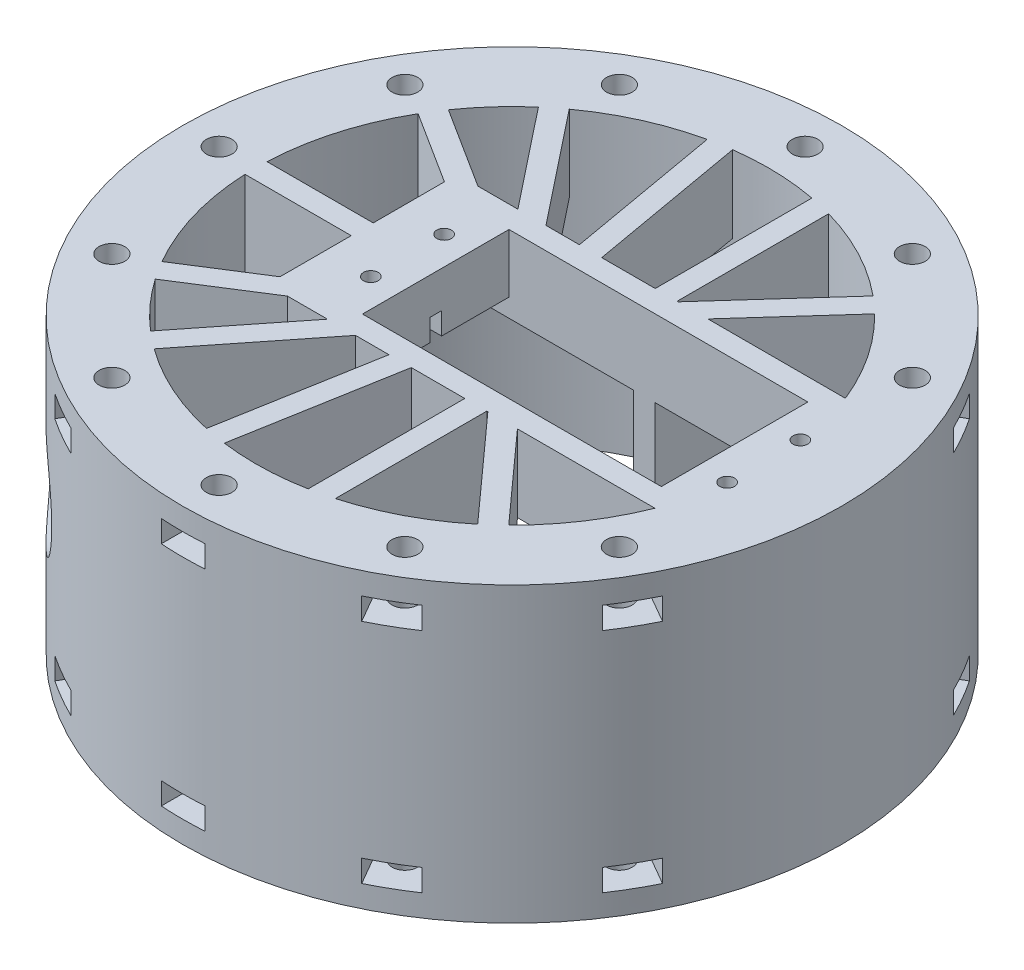
SolidWorks part; units mm, degrees
ref_plane "Front Plane" through (0, 0, 0) normal (0, 0, 1) x (1, 0, 0)
ref_plane "Top Plane" through (0, 0, 0) normal (0, 1, 0) x (1, 0, 0)
ref_plane "Right Plane" through (0, 0, 0) normal (1, 0, 0) x (0, 0, -1)
sketch "Sketch1" plane through (0, 0, 0) normal (0, 1, 0) x (1, 0, 0)
  line L0 (-43.0464, 0) -> (41.9462, 0) construction
  line L1 (0, 43.1152) -> (0, -41.8775) construction
  circle A1 centre (0, 0) radius 45
  dimension "D2" = 90
extrude "Boss-Extrude1" add sketch "Sketch1" along normal blind 40
sketch "Sketch2" plane through (0, 0, 0) normal (0, -1, 0) x (1, 0, 0)
  circle A0 centre (0, 0) radius 35
  dimension "D1" = 70
extrude "Cut-Extrude1" cut sketch "Sketch2" against normal blind 29.5
sketch "Sketch3" plane through (0, 29.5, 0) normal (0, -1, 0) x (1, 0, 0)
  line L0 (35, 0) -> (-35, 0) construction
  line L1 (0, -35) -> (0, 35) construction
  line L3 (37.5324, -10) -> (-17.4676, -10)
  line L4 (37.5324, -10) -> (37.5324, 10)
  line L5 (37.5324, 10) -> (-17.4676, 10)
  line L6 (-17.4676, -10) -> (-17.4676, 10)
  circle A0 centre (0, 0) radius 35 construction
  circle A1 centre (0, 0) radius 35 construction
  dimension "D1" = 20
  dimension "D2" = 55
  dimension "D3" = 10
  dimension "D4" = 37.5324
extrude "Cut-Extrude2" cut sketch "Sketch3" against normal blind 2.5 and the other way up to next
sketch "Sketch4" plane through (0, 32, 0) normal (0, -1, 0) x (1, 0, 0)
  line L0 (37.5324, 0) -> (-17.4676, 0) construction
  line L1 (37.5324, 10) -> (37.5324, -10) construction
  line L2 (-17.4676, 10) -> (-17.4676, -10) construction
  line L3 (0, -10) -> (0, 10) construction
  line L4 (-17.4676, -10) -> (33.541, -10) construction
  line L5 (33.541, 10) -> (-17.4676, 10) construction
  line L7 (30.3722, -10) -> (-10.4278, -10)
  line L8 (30.3722, -10) -> (30.3722, 10)
  line L9 (30.3722, 10) -> (-10.4278, 10)
  line L10 (-10.4278, -10) -> (-10.4278, 10)
  dimension "D1" = 20
  dimension "D2" = 40.8
  dimension "D3" = 30.3722
  dimension "D4" = 10
extrude "Cut-Extrude3" cut sketch "Sketch4" against normal blind 9
sketch "Sketch8" plane through (0, 29.5, 0) normal (0, -1, 0) x (1, 0, 0)
  line L0 (-17.4676, 0) -> (-35, 0) construction
  line L1 (-17.4676, 10) -> (-17.4676, -10) construction
  line L2 (8.0367, 10) -> (8.0367, 34.0648) construction
  line L3 (33.541, 10) -> (-17.4676, 10) construction
  line L4 (8.0367, -10) -> (8.0367, -29.3194) construction
  line L5 (-17.4676, -10) -> (33.541, -10) construction
  line L6 (6.5367, 10) -> (6.5367, 34.3842)
  line L7 (9.5367, 10) -> (9.5367, 33.6757)
  line L8 (9.5367, 10) -> (6.5367, 10)
  line L9 (9.5367, -10) -> (6.5367, -10)
  line L10 (6.5367, -10) -> (6.5367, -34.3842)
  line L11 (9.5367, -10) -> (9.5367, -33.6757)
  line L12 (-17.4676, 1.5) -> (-34.9678, 1.5)
  line L13 (-17.4676, -1.5) -> (-34.9678, -1.5)
  line L14 (-17.4676, 1.5) -> (-17.4676, -1.5)
  arc A0 (33.541, 10) -> (33.541, -10) centre (0, 0) ccw construction
  arc A1 (9.5367, 33.6757) -> (6.5367, 34.3842) centre (7.9531, 33.6757) ccw
  arc A2 (9.5367, -33.6757) -> (6.5367, -34.3842) centre (7.9531, -33.6757) cw
  arc A3 (-34.9678, 1.5) -> (-34.9678, -1.5) centre (-34.9678, 0) ccw
  dimension "D3" = 1.5
  dimension "D1" = 1.5
  dimension "D2" = 1.5
  dimension "D4" = 1.5
extrude "Boss-Extrude2" add sketch "Sketch8" along normal through all
sketch "Sketch16" plane through (0, 32, 0) normal (0, -1, 0) x (1, 0, 0)
  line L0 (-17.4676, 0) -> (37.5324, 0) construction
  line L1 (-17.4676, 10) -> (-17.4676, -10) construction
  line L2 (37.5324, -10) -> (37.5324, 10) construction
  line L3 (30.3722, -0.8) -> (37.5324, -0.8)
  line L4 (-10.4278, -0.8) -> (-17.4676, -0.8)
  line L5 (-10.4278, 10) -> (-10.4278, -10) construction
  line L6 (-10.4278, 0.8) -> (-17.4676, 0.8)
  line L7 (-17.4676, 0.8) -> (-17.4676, -0.8)
  line L8 (-10.4278, 0.8) -> (-10.4278, -0.8)
  line L9 (30.3722, -10) -> (30.3722, 10) construction
  line L10 (30.3722, 0.8) -> (37.5324, 0.8)
  line L11 (37.5324, 0.8) -> (37.5324, -0.8)
  line L12 (30.3722, 0.8) -> (30.3722, -0.8)
  dimension "D1" = 0.8
extrude "Cut-Extrude10" cut sketch "Sketch16" against normal blind 3
sketch "Sketch27" plane through (0, 0, 0) normal (0, -1, 0) x (1, 0, 0)
  line L0 (0, 0) -> (0, -53.17) construction
  line L1 (0, 0) -> (47.7582, -27.5732) construction
  line L3 (31.641, -18.2679) -> (31.641, -21.7321) construction
  line L4 (31.641, -21.7321) -> (34.641, -23.4641) construction
  line L5 (34.641, -23.4641) -> (37.641, -21.7321) construction
  line L6 (37.641, -21.7321) -> (37.641, -18.2679) construction
  line L7 (37.641, -18.2679) -> (34.641, -16.5359) construction
  line L8 (34.641, -16.5359) -> (31.641, -18.2679) construction
  circle A0 centre (0, 0) radius 40 construction
  circle A1 centre (34.641, -20) radius 1.75
  circle A2 centre (0, 0) radius 35 construction
  circle A3 centre (34.641, -20) radius 3 construction
  circle A4 centre (20, -34.641) radius 1.75
  circle A5 centre (0, -40) radius 1.75
  circle A6 centre (-20, -34.641) radius 1.75
  circle A7 centre (-34.641, -20) radius 1.75
  circle A8 centre (-40, 0) radius 1.75
  circle A9 centre (-34.641, 20) radius 1.75
  circle A10 centre (-20, 34.641) radius 1.75
  circle A11 centre (0, 40) radius 1.75
  circle A12 centre (20, 34.641) radius 1.75
  circle A13 centre (34.641, 20) radius 1.75
  circle A15 centre (40, 0) radius 1.75 [skipped]
  point P28 (0, 0)
  point P41 (0, 0)
  dimension "D1" = 80
  dimension "D3" = 3.5
  dimension "D4" = 70
  dimension "D5" = 6
  dimension "D6" = 12
  dimension "D2" = 60
extrude "Cut-Extrude15" cut sketch "Sketch27" against normal through all
ref_plane "Plane1" through (0, 37, 0) normal (0, 1, 0) x (1, 0, 0)
sketch "Sketch28" plane through (0, 37, 0) normal (0, 1, 0) x (1, 0, 0)
  line L0 (0, 0) -> (-54.493, 0) construction
  line L1 (-31.641, 18.2679) -> (-31.641, 21.7321)
  line L2 (-36.5359, 0) -> (-38.2679, 3)
  line L3 (-38.2679, 3) -> (-44.8999, 3)
  line L4 (-31.641, 21.7321) -> (-37.3844, 25.048)
  line L5 (-40.3844, 19.8519) -> (-34.641, 16.5359)
  line L6 (-44.8999, -3) -> (-38.2679, -3)
  line L7 (-38.2679, -3) -> (-36.5359, 0)
  line L8 (-43.4641, 0) -> (-42.5981, -1.5) [skipped]
  line L9 (-41.7321, 3) -> (-42.5981, 1.5) [skipped]
  line L10 (-34.641, 16.5359) -> (-31.641, 18.2679)
  line L11 (-18.2679, 31.641) -> (-16.5359, 34.641)
  line L12 (-16.5359, 34.641) -> (-19.8519, 40.3844)
  line L13 (-25.048, 37.3844) -> (-21.7321, 31.641)
  line L14 (-21.7321, 31.641) -> (-18.2679, 31.641)
  line L15 (0, 36.5359) -> (3, 38.2679)
  line L16 (3, 38.2679) -> (3, 44.8999)
  line L17 (-3, 44.8999) -> (-3, 38.2679)
  line L18 (-3, 38.2679) -> (0, 36.5359)
  line L19 (18.2679, 31.641) -> (21.7321, 31.641)
  line L20 (21.7321, 31.641) -> (25.048, 37.3844)
  line L21 (19.8519, 40.3844) -> (16.5359, 34.641)
  line L22 (16.5359, 34.641) -> (18.2679, 31.641)
  line L23 (31.641, 18.2679) -> (34.641, 16.5359)
  line L24 (34.641, 16.5359) -> (40.3844, 19.8519)
  line L25 (37.3844, 25.048) -> (31.641, 21.7321)
  line L26 (31.641, 21.7321) -> (31.641, 18.2679)
  line L31 (31.641, -18.2679) -> (31.641, -21.7321)
  line L32 (31.641, -21.7321) -> (37.3844, -25.048)
  line L33 (40.3844, -19.8519) -> (34.641, -16.5359)
  line L34 (34.641, -16.5359) -> (31.641, -18.2679)
  line L35 (18.2679, -31.641) -> (16.5359, -34.641)
  line L36 (16.5359, -34.641) -> (19.8519, -40.3844)
  line L37 (25.048, -37.3844) -> (21.7321, -31.641)
  line L38 (21.7321, -31.641) -> (18.2679, -31.641)
  line L39 (0, -36.5359) -> (-3, -38.2679)
  line L40 (-3, -38.2679) -> (-3, -44.8999)
  line L41 (3, -44.8999) -> (3, -38.2679)
  line L42 (3, -38.2679) -> (0, -36.5359)
  line L43 (-18.2679, -31.641) -> (-21.7321, -31.641)
  line L44 (-21.7321, -31.641) -> (-25.048, -37.3844)
  line L45 (-19.8519, -40.3844) -> (-16.5359, -34.641)
  line L46 (-16.5359, -34.641) -> (-18.2679, -31.641)
  line L47 (-31.641, -18.2679) -> (-34.641, -16.5359)
  line L48 (-34.641, -16.5359) -> (-40.3844, -19.8519)
  line L49 (-37.3844, -25.048) -> (-31.641, -21.7321)
  line L50 (-31.641, -21.7321) -> (-31.641, -18.2679)
  line L51 (36.5359, 0) -> (38.2679, -3) [skipped]
  line L52 (38.2679, -3) -> (44.8999, -3) [skipped]
  line L53 (44.8999, 3) -> (38.2679, 3) [skipped]
  line L54 (38.2679, 3) -> (36.5359, 0) [skipped]
  arc A0 (-44.8999, 3) -> (-44.8999, -3) centre (0, 0) ccw
  circle A1 centre (-40, 0) radius 3 construction
  arc A2 (-37.3844, 25.048) -> (-40.3844, 19.8519) centre (0, 0) ccw
  circle A3 centre (-34.641, 20) radius 3 construction
  arc A4 (-19.8519, 40.3844) -> (-25.048, 37.3844) centre (0, 0) ccw
  circle A5 centre (-20, 34.641) radius 3 construction
  arc A6 (3, 44.8999) -> (-3, 44.8999) centre (0, 0) ccw
  circle A7 centre (0, 40) radius 3 construction
  arc A8 (25.048, 37.3844) -> (19.8519, 40.3844) centre (0, 0) ccw
  circle A9 centre (20, 34.641) radius 3 construction
  arc A10 (40.3844, 19.8519) -> (37.3844, 25.048) centre (0, 0) ccw
  circle A11 centre (34.641, 20) radius 3 construction
  arc A14 (37.3844, -25.048) -> (40.3844, -19.8519) centre (0, 0) ccw
  circle A15 centre (34.641, -20) radius 3 construction
  arc A16 (19.8519, -40.3844) -> (25.048, -37.3844) centre (0, 0) ccw
  circle A17 centre (20, -34.641) radius 3 construction
  arc A18 (-3, -44.8999) -> (3, -44.8999) centre (0, 0) ccw
  circle A19 centre (0, -40) radius 3 construction
  arc A20 (-25.048, -37.3844) -> (-19.8519, -40.3844) centre (0, 0) ccw
  circle A21 centre (-20, -34.641) radius 3 construction
  arc A22 (-40.3844, -19.8519) -> (-37.3844, -25.048) centre (0, 0) ccw
  circle A23 centre (-34.641, -20) radius 3 construction
  arc A24 (44.8999, -3) -> (44.8999, 3) centre (0, 0) ccw [skipped]
  circle A25 centre (40, 0) radius 3 construction
  point P94 (0, 0)
  dimension "D1" = 90
  dimension "D2" = 6
  dimension "D3" = 12
extrude "Cut-Extrude17" cut sketch "Sketch28" against normal blind 3
sketch "Sketch29" plane through (0, 29.5, 0) normal (0, -1, 0) x (1, 0, 0)
  line L0 (32.4962, -13) -> (13.7255, -13)
  line L1 (9.5367, -33.6757) -> (9.5367, -10) construction
  line L2 (9.5367, -13) -> (9.5367, -33.6757)
  line L3 (9.5367, -10) -> (33.541, -10) construction
  line L4 (6.5367, -13) -> (-0.7691, -13)
  line L5 (6.5367, -10) -> (6.5367, -34.3842) construction
  line L6 (-20.4676, -11.223) -> (-20.4676, -1.5)
  line L7 (-34.9678, -1.5) -> (-17.4676, -1.5) construction
  line L8 (-20.4676, -1.5) -> (-34.9678, -1.5)
  line L9 (-17.4676, -0.8) -> (-17.4676, -10) construction
  line L10 (32.4962, 13) -> (13.7255, 13)
  line L11 (9.5367, 10) -> (9.5367, 33.6757) construction
  line L12 (9.5367, 13) -> (9.5367, 33.6757)
  line L13 (-7.5493, 34.1761) -> (-3.8154, 13)
  line L14 (6.5367, 13) -> (-0.7691, 13)
  line L15 (6.5367, 34.3842) -> (6.5367, 10) construction
  line L16 (-20.4676, 11.223) -> (-20.4676, 1.5)
  line L17 (-17.4676, 1.5) -> (-34.9678, 1.5) construction
  line L18 (-20.4676, 1.5) -> (-34.9678, 1.5)
  line L19 (6.5367, 13) -> (6.5367, 34.3842)
  line L20 (6.5367, -34.3842) -> (6.5367, -13)
  line L21 (0, 0) -> (-21.7353, -27.4331) construction
  line L22 (-20.5397, -28.3394) -> (-8.3862, -13)
  line L23 (-22.8911, -26.4764) -> (-12.2137, -13)
  line L24 (0, 0) -> (-20.4676, -13) construction
  line L25 (-17.6698, -13) -> (-28.713, -20.0141)
  line L26 (-20.4676, -11.223) -> (-30.3215, -17.4817)
  line L27 (0, 0) -> (-35, 0) construction
  line L28 (-20.4676, 11.223) -> (-30.3215, 17.4817)
  line L29 (-17.6698, 13) -> (-28.713, 20.0141)
  line L30 (-22.8911, 26.4764) -> (-12.2137, 13)
  line L31 (-20.5397, 28.3394) -> (-8.3862, 13)
  line L32 (-12.2137, 13) -> (-17.6698, 13)
  line L33 (0, 0) -> (-6.0777, -34.4683) construction
  line L34 (-4.5949, -34.6971) -> (-0.7691, -13)
  line L35 (-7.5493, -34.1761) -> (-3.8154, -13)
  line L36 (-3.8154, -13) -> (-17.6698, -13)
  line L37 (-4.5949, 34.6971) -> (-0.7691, 13)
  line L38 (-3.8154, 13) -> (-8.3862, 13)
  line L39 (0, 0) -> (23.4214, -26.0084) construction
  line L40 (9.6883, -13) -> (22.2852, -26.9883)
  line L41 (13.7255, -13) -> (24.5145, -24.9808)
  line L42 (13.7255, 13) -> (24.5145, 24.9808)
  line L43 (9.6883, 13) -> (22.2852, 26.9883)
  line L44 (9.6883, -13) -> (9.5367, -13)
  line L45 (9.6883, 13) -> (9.5367, 13)
  arc A0 (9.5367, -33.6757) -> (22.2852, -26.9883) centre (0, 0) ccw
  arc A1 (6.5367, 34.3842) -> (-4.5949, 34.6971) centre (0, 0) ccw
  arc A2 (32.4962, 13) -> (24.5145, 24.9808) centre (0, 0) ccw
  arc A3 (-34.9678, -1.5) -> (-30.3215, -17.4817) centre (0, 0) ccw
  circle A4 centre (0, 0) radius 35 construction
  arc A5 (-7.5493, 34.1761) -> (-20.5397, 28.3394) centre (0, 0) ccw
  arc A6 (-4.5949, -34.6971) -> (6.5367, -34.3842) centre (0, 0) ccw
  arc A7 (-20.5397, -28.3394) -> (-7.5493, -34.1761) centre (0, 0) ccw
  arc A8 (-28.713, -20.0141) -> (-22.8911, -26.4764) centre (0, 0) ccw
  arc A9 (-30.3215, 17.4817) -> (-34.9678, 1.5) centre (0, 0) ccw
  arc A10 (-22.8911, 26.4764) -> (-28.713, 20.0141) centre (0, 0) ccw
  arc A11 (24.5145, -24.9808) -> (32.4962, -13) centre (0, 0) ccw
  arc A12 (22.2852, 26.9883) -> (9.5367, 33.6757) centre (0, 0) ccw
  point P11 (21.5389, -10)
  point P23 (-17.4676, -5.4)
  line M3 (-17.4676, -1.5) -> (-34.9678, -1.5)
  arc M4 (-34.9678, -1.5) -> (6.5367, -34.3842) centre (0, 0) ccw
  line M5 (6.5367, -34.3842) -> (6.5367, -10)
  dimension "D1" = 1.5
  dimension "D2" = 3
  dimension "D3" = 3
  dimension "D4" = 80
  dimension "D5" = 1.5
  dimension "D6" = 1.5
  dimension "D7" = 1.5
sketch "Sketch32" plane through (0, 32, 0) normal (0, -1, 0) x (1, 0, 0)
  line L0 (-17.4676, 0) -> (37.5324, 0) construction
  line L1 (-17.4676, -1.5) -> (-17.4676, 1.5) construction
  line L2 (37.5324, 10) -> (37.5324, -10) construction
  line L3 (10.0324, 0) -> (10.0324, -10) construction
  line L6 (9.5367, -10) -> (33.541, -10) construction
  circle A0 centre (-14.2876, -5) radius 1
  circle A1 centre (-14.2876, 5) radius 1
  circle A2 centre (34.3524, -5) radius 1
  circle A3 centre (34.3524, 5) radius 1
  dimension "D1" = 24.32
  dimension "D3" = 2
  dimension "D2" = 5
extrude "Cut-Extrude21" cut sketch "Sketch32" against normal through all
extrude "Cut-Extrude22" cut sketch "Sketch29" against normal blind 12 contours L28 A9 L18 L16 | L26 L6 M3 M4 | L23 L36 L25 M4 | L35 L36 L22 M4 | L34 L4 M4 M5 | L2 A0 L40 L44 | L41 A11 L0 | L10 A2 L42 | L43 A12 L12 L45 | L19 A1 L37 L14 | L13 A5 L31 L38 | L30 A10 L29 L32 region at (23.89, 29.5, -17.1237) region at (13.9029, 29.5, -24.813) region at (1.8383, 29.5, -24.6789) region at (-27.5459, 29.5, -7.8919) region at (-10.8152, 29.5, -24.1049) region at (-20.9968, 29.5, -18.9781) region at (23.89, 29.5, 17.1237) region at (13.9029, 29.5, 24.813) region at (-10.8152, 29.5, 24.1049) region at (1.8383, 29.5, 24.6789) region at (-27.5459, 29.5, 7.8919) region at (-20.9968, 29.5, 18.9781)
sketch "Sketch33" plane through (0, 0, 1.5) normal (0, 0, 1) x (1, 0, 0)
  line L0 (-17.4676, 14.75) -> (-34.9678, 0)
  line L1 (-17.4676, 0) -> (-17.4676, 29.5) construction
  line L2 (-34.9678, 0) -> (-17.4676, 0)
  line L3 (-17.4676, 0) -> (-34.9678, 0) construction
  line L4 (-17.4676, 0) -> (-17.4676, 14.75)
extrude "Cut-Extrude23" cut sketch "Sketch33" against normal up to next
ref_plane "Plane2" through (0, 3, 0) normal (0, -1, 0) x (-1, 0, 0)
sketch "Sketch34" plane through (0, 3, 0) normal (0, -1, 0) x (-1, 0, 0)
  line L0 (0, 0) -> (0, 45) construction
  line L1 (18.2679, 31.641) -> (21.7321, 31.641)
  line L2 (0, 36.5359) -> (3, 38.2679)
  line L3 (3, 38.2679) -> (3, 44.8999)
  line L4 (21.7321, 31.641) -> (25.048, 37.3844)
  line L5 (19.8519, 40.3844) -> (16.5359, 34.641)
  line L6 (-3, 44.8999) -> (-3, 38.2679)
  line L7 (-3, 38.2679) -> (0, 36.5359)
  line L8 (0, 43.4641) -> (-1.5, 42.5981) [skipped]
  line L9 (3, 41.7321) -> (1.5, 42.5981) [skipped]
  line L10 (16.5359, 34.641) -> (18.2679, 31.641)
  line L11 (31.641, 18.2679) -> (34.641, 16.5359)
  line L12 (34.641, 16.5359) -> (40.3844, 19.8519)
  line L13 (37.3844, 25.048) -> (31.641, 21.7321)
  line L14 (31.641, 21.7321) -> (31.641, 18.2679)
  line L15 (36.5359, 0) -> (38.2679, -3)
  line L16 (38.2679, -3) -> (44.8999, -3)
  line L17 (44.8999, 3) -> (38.2679, 3)
  line L18 (38.2679, 3) -> (36.5359, 0)
  line L19 (31.641, -18.2679) -> (31.641, -21.7321)
  line L20 (31.641, -21.7321) -> (37.3844, -25.048)
  line L21 (40.3844, -19.8519) -> (34.641, -16.5359)
  line L22 (34.641, -16.5359) -> (31.641, -18.2679)
  line L23 (18.2679, -31.641) -> (16.5359, -34.641)
  line L24 (16.5359, -34.641) -> (19.8519, -40.3844)
  line L25 (25.048, -37.3844) -> (21.7321, -31.641)
  line L26 (21.7321, -31.641) -> (18.2679, -31.641)
  line L27 (0, -36.5359) -> (-3, -38.2679)
  line L28 (-3, -38.2679) -> (-3, -44.8999)
  line L29 (3, -44.8999) -> (3, -38.2679)
  line L30 (3, -38.2679) -> (0, -36.5359)
  line L31 (-18.2679, -31.641) -> (-21.7321, -31.641)
  line L32 (-21.7321, -31.641) -> (-25.048, -37.3844)
  line L33 (-19.8519, -40.3844) -> (-16.5359, -34.641)
  line L34 (-16.5359, -34.641) -> (-18.2679, -31.641)
  line L35 (-31.641, -18.2679) -> (-34.641, -16.5359)
  line L36 (-34.641, -16.5359) -> (-40.3844, -19.8519)
  line L37 (-37.3844, -25.048) -> (-31.641, -21.7321)
  line L38 (-31.641, -21.7321) -> (-31.641, -18.2679)
  line L43 (-31.641, 18.2679) -> (-31.641, 21.7321)
  line L44 (-31.641, 21.7321) -> (-37.3844, 25.048)
  line L45 (-40.3844, 19.8519) -> (-34.641, 16.5359)
  line L46 (-34.641, 16.5359) -> (-31.641, 18.2679)
  line L47 (-18.2679, 31.641) -> (-16.5359, 34.641)
  line L48 (-16.5359, 34.641) -> (-19.8519, 40.3844)
  line L49 (-25.048, 37.3844) -> (-21.7321, 31.641)
  line L50 (-21.7321, 31.641) -> (-18.2679, 31.641)
  line L51 (-36.5359, 0) -> (-38.2679, 3) [skipped]
  line L52 (-38.2679, 3) -> (-44.8999, 3) [skipped]
  line L53 (-44.8999, -3) -> (-38.2679, -3) [skipped]
  line L54 (-38.2679, -3) -> (-36.5359, 0) [skipped]
  circle A0 centre (0, 0) radius 45 construction
  circle A1 centre (0, 40) radius 3 construction
  arc A2 (3, 44.8999) -> (-3, 44.8999) centre (0, 0) ccw
  arc A3 (25.048, 37.3844) -> (19.8519, 40.3844) centre (0, 0) ccw
  circle A4 centre (20, 34.641) radius 3 construction
  arc A5 (40.3844, 19.8519) -> (37.3844, 25.048) centre (0, 0) ccw
  circle A6 centre (34.641, 20) radius 3 construction
  arc A7 (44.8999, -3) -> (44.8999, 3) centre (0, 0) ccw
  circle A8 centre (40, 0) radius 3 construction
  arc A9 (37.3844, -25.048) -> (40.3844, -19.8519) centre (0, 0) ccw
  circle A10 centre (34.641, -20) radius 3 construction
  arc A11 (19.8519, -40.3844) -> (25.048, -37.3844) centre (0, 0) ccw
  circle A12 centre (20, -34.641) radius 3 construction
  arc A13 (-3, -44.8999) -> (3, -44.8999) centre (0, 0) ccw
  circle A14 centre (0, -40) radius 3 construction
  arc A15 (-25.048, -37.3844) -> (-19.8519, -40.3844) centre (0, 0) ccw
  circle A16 centre (-20, -34.641) radius 3 construction
  arc A17 (-40.3844, -19.8519) -> (-37.3844, -25.048) centre (0, 0) ccw
  circle A18 centre (-34.641, -20) radius 3 construction
  arc A21 (-37.3844, 25.048) -> (-40.3844, 19.8519) centre (0, 0) ccw
  circle A22 centre (-34.641, 20) radius 3 construction
  arc A23 (-19.8519, 40.3844) -> (-25.048, 37.3844) centre (0, 0) ccw
  circle A24 centre (-20, 34.641) radius 3 construction
  arc A25 (-44.8999, 3) -> (-44.8999, -3) centre (0, 0) ccw [skipped]
  circle A26 centre (-40, 0) radius 3 construction
  point P98 (0, 0)
  dimension "D1" = 6
  dimension "D2" = 90
  dimension "D3" = 12
extrude "Cut-Extrude24" cut sketch "Sketch34" against normal blind 3
ref_plane "Plane3" through (4.0184, 0, -4.0184) normal (0.7071, 0, -0.7071) x (-0.7071, 0, -0.7071)
sketch "Sketch35" plane through (4.0184, 0, -4.0184) normal (0.7071, 0, -0.7071) x (-0.7071, 0, -0.7071)
  line L0 (-8.7232, 6) -> (8.6028, 6) construction
  line L1 (-8.7232, 34) -> (8.7232, 34) construction
  line L2 (-0.0602, 6) -> (0, 34) construction
  circle A0 centre (-0.0301, 20) radius 7
  dimension "D1" = 14
extrude "Cut-Extrude25" cut sketch "Sketch35" against normal through all
